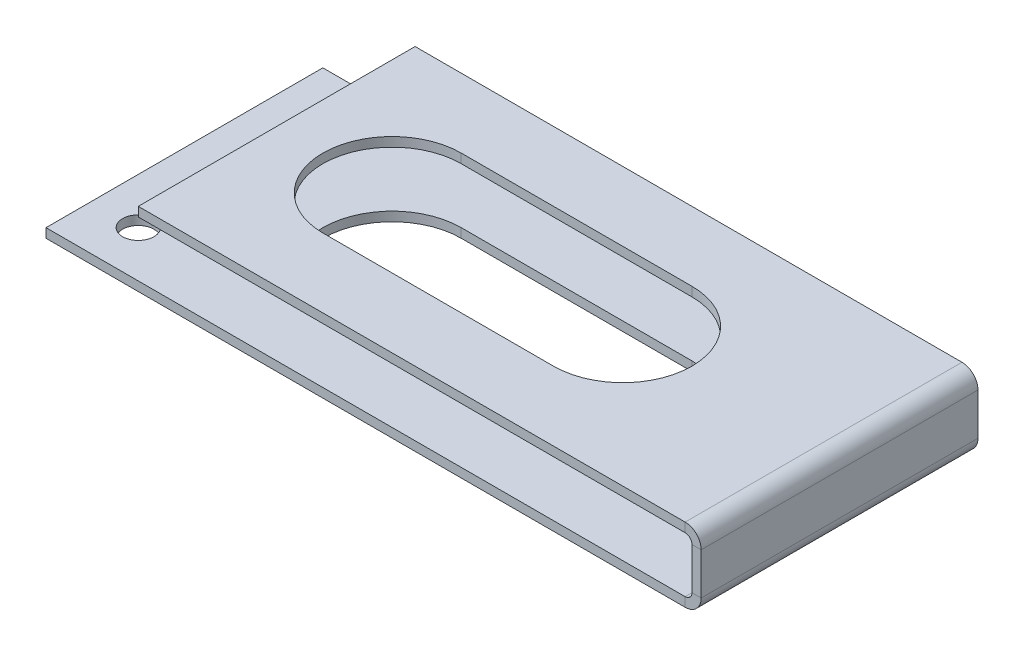
SolidWorks part; units mm, degrees
note: The reader was unsure of these and kept them because the rebuilt part matched: flange length of "Tôle pliée sur arête1", "Tôle pliée sur arête2".
ref_plane "Plan de face" through (0, 0, 0) normal (0, 0, 1) x (1, 0, 0)
ref_plane "Plan de dessus" through (0, 0, 0) normal (0, 1, 0) x (1, 0, 0)
ref_plane "Plan de droite" through (0, 0, 0) normal (1, 0, 0) x (0, 0, -1)
sketch "Esquisse2" plane through (0, 0, 0) normal (0, 1, 0) x (1, 0, 0)
  line L1 (-30, -15) -> (30, -15)
  line L2 (-30, -15) -> (-30, 15)
  line L3 (-30, 15) -> (30, 15)
  line L4 (30, -15) -> (30, 15)
  line L5 (-30, -15) -> (30, 15) construction
  line L6 (-30, 15) -> (30, -15) construction
  line L9 (-7.8646, 0) -> (7.8646, 0) construction
  point P0 (0, 0)
  dimension "D130" = 30
  dimension "D2" = 60
base flange "Tôle de base pliée1" sketch "Esquisse2" thickness 1 reverse thickness direction no parameters "D1"=0.7366
edge flange "Tôle pliée sur arête1" sketch "Esquisse9" flange angle 90 flange length 6 flange position material outside bend radius 0.7366 thickness 1 relief rectangular parameters "D6"=10
sketch "Esquisse9" plane through (30, -1, 0) normal (1, 0, 0) x (0, 0, 1)
  line L2 (-15, 0) -> (-15, 6)
  line L3 (-15, 6) -> (15, 6)
  line L4 (15, 6) -> (15, 0)
  line L7 (15, 0) -> (-15, 0) construction
  line L8 (15, 0) -> (-15, 0)
bend "Pli d'arête1" bend radius 0.7366 bend angle 90 parameters "D5"=1
edge flange "Tôle pliée sur arête2" sketch "Esquisse12" flange angle 90 flange length 70 flange position material outside bend radius 0.7366 thickness 1 relief rectangular parameters "D6"=10
sketch "Esquisse12" plane through (30, -7, 0) normal (0, -1, 0) x (0, 0, 1)
  line L0 (15, 0) -> (-15, 0) construction
  line L1 (15, 0) -> (-15, 0)
  line L2 (-15, 0) -> (-15, 70)
  line L3 (-15, 70) -> (15, 70)
  line L4 (15, 70) -> (15, 0)
bend "Pli d'arête2" bend radius 0.7366 bend angle 90 parameters "D5"=2
sketch "Esquisse26" plane through (0, 0, 0) normal (0, 1, 0) x (1, 0, 0)
  line L0 (-17.5, 0) -> (7.5, 0) construction
  line L1 (-7.8646, 0) -> (7.8646, 0) construction
  line L2 (-17.5, 7.5) -> (7.5, 7.5)
  line L3 (-17.5, -7.5) -> (7.5, -7.5)
  line L5 (-30, 15) -> (-30, -15) construction
  arc A0 (-17.5, 7.5) -> (-17.5, -7.5) centre (-17.5, 0) ccw
  arc A1 (7.5, -7.5) -> (7.5, 7.5) centre (7.5, 0) ccw
  point P5 (-5, 0)
  point P10 (-25, 0)
  point P11 (15, 0)
  dimension "D1" = 40
  dimension "D2" = 15
  dimension "D3" = 5
extrude "Enlèv. mat.-Extru.1" cut sketch "Esquisse26" against normal through all normal cut yes
sketch "Esquisse27" plane through (0, -8, 0) normal (0, 1, 0) x (1, 0, 0)
  line L0 (-35, 15) -> (-35, -15) construction
  line L1 (-30, 15) -> (30, 15) construction
  line L2 (-30, -15) -> (29.2634, -15) construction
  line L3 (-7.8646, 0) -> (7.8646, 0) construction
  line L5 (29.2634, 15) -> (-30, 15) construction
  line L6 (-40, -15) -> (-40, 15) construction
  circle A0 centre (-35, 10) radius 1.7
  circle A1 centre (-35, -10) radius 1.7
  dimension "D2" = 3.4
  dimension "D3" = 5
  dimension "D1" = 5
extrude "Enlèv. mat.-Extru.2" cut sketch "Esquisse27" along normal up to next normal cut yes
sketch "Esquisse29" plane through (0, -7, 0) normal (0, 1, 0) x (1, 0, 0)
  line L0 (-7.8646, 0) -> (7.8646, 0) construction
  line L1 (31, -15) -> (31, 15) construction
  circle A0 centre (26, 0) radius 1.7
  dimension "D1" = 3.4
  dimension "D2" = 5
extrude "Enlèv. mat.-Extru.3" cut sketch "Esquisse29" against normal through all normal cut yes
sketch "Esquisse30" plane through (0, -8, 0) normal (0, -1, 0) x (1, 0, 0)
  line L0 (-5, 7.5) -> (-5, -7.5) construction
  line L1 (-17.5, 7.5) -> (7.5, 7.5) construction
  line L2 (7.5, -7.5) -> (-17.5, -7.5) construction
sketch3d "Esquisse3D2"
  line L0 (-5, -8, 7.5) -> (-5, -8, -7.5) construction
sketch "Lignes de pliage1" [suppressed] plane through (0, 0, 0) normal (0, 1, 0) x (1, 0, 0)
sketch "Cube de visualisation1" [suppressed] plane through (0, 0, 0) normal (0, 1, 0) x (1, 0, 0)
sheet metal parameters "Tôlerie1" thickness 1 parameters "D1"=0.7366
flat pattern "Etat déplié1" [suppressed]
sketch "Lignes de pliage2" plane through (0, 0, 0) normal (0, 1, 0) x (1, 0, 0)
sketch3d "Cube de visualisation2" [suppressed]
  line L0 (-26.75, 15, 0) -> (26.75, 15, 0) construction
  line L1 (-26.75, -15, 0) -> (26.75, -15, 0) construction
  line L2 (-26.75, 15, 0) -> (-26.75, -15, 0) construction
  line L3 (26.75, 15, 0) -> (26.75, -15, 0) construction
sheet metal parameters "Tôlerie2" thickness 1 parameters "D1"=0.7366
flat pattern "Etat déplié1"
sketch "Lignes de pliage2" plane through (0, 0, 0) normal (0, 1, 0) x (1, 0, 0)
  line L0 (26.9846, -15) -> (26.9846, 15) construction
  line L1 (26.9846, -15) -> (26.9846, 15) construction
sketch3d "Cube de visualisation2" [suppressed]
  line L0 (32.2192, 15, 0) -> (-26.75, 15, 0) construction
  line L1 (32.2192, -15, 0) -> (-26.75, -15, 0) construction
  line L2 (32.2192, 15, 0) -> (32.2192, -15, 0) construction
  line L3 (-26.75, 15, 0) -> (-26.75, -15, 0) construction
bend of the flat pattern "Dépliage-<Pli d'arête1>1"
sheet metal parameters "Tôlerie3" thickness 1 parameters "D1"=0.7366
flat pattern "Etat déplié1"
sketch "Lignes de pliage2" plane through (0, 0, 0) normal (0, 1, 0) x (1, 0, 0)
  line L0 (26.9846, -15) -> (26.9846, 15) construction
  line L1 (26.9846, -15) -> (26.9846, 15) construction
  line L2 (32.4539, -15) -> (32.4539, 15) construction
  line L3 (32.4539, -15) -> (32.4539, 15) construction
sketch3d "Cube de visualisation2" [suppressed]
  line L0 (86.1885, 15, 0) -> (-26.75, 15, 0) construction
  line L1 (86.1885, -15, 0) -> (-26.75, -15, 0) construction
  line L2 (86.1885, 15, 0) -> (86.1885, -15, 0) construction
  line L3 (-26.75, 15, 0) -> (-26.75, -15, 0) construction
bend of the flat pattern "Dépliage-<Pli d'arête1>1"
bend of the flat pattern "Dépliage-<Pli d'arête2>1"
sheet metal parameters "Tôlerie7" thickness 1 parameters "D1"=0.7366
flat pattern "Etat déplié1"
sketch "Lignes de pliage2" plane through (0, 0, 0) normal (0, 1, 0) x (1, 0, 0)
  line L0 (26.9846, -15) -> (26.9846, 15) construction
  line L1 (26.9846, -15) -> (26.9846, 15) construction
  line L2 (32.4539, -15) -> (32.4539, 15) construction
  line L3 (32.4539, -15) -> (32.4539, 15) construction
sketch3d "Cube de visualisation2" [suppressed]
  line L0 (86.1885, 15, 0) -> (-26.75, 15, 0) construction
  line L1 (86.1885, -15, 0) -> (-26.75, -15, 0) construction
  line L2 (86.1885, 15, 0) -> (86.1885, -15, 0) construction
  line L3 (-26.75, 15, 0) -> (-26.75, -15, 0) construction
bend of the flat pattern "Dépliage-<Pli d'arête1>1"
bend of the flat pattern "Dépliage-<Pli d'arête2>1"
sheet metal parameters "Tôlerie8" thickness 1 parameters "D1"=0.7366
flat pattern "Etat déplié1"
sketch "Lignes de pliage2" plane through (0, 0, 0) normal (0, 1, 0) x (1, 0, 0)
  line L0 (26.9846, -15) -> (26.9846, 15) construction
  line L1 (26.9846, -15) -> (26.9846, 15) construction
  line L2 (32.4539, -15) -> (32.4539, 15) construction
  line L3 (32.4539, -15) -> (32.4539, 15) construction
sketch3d "Cube de visualisation2" [suppressed]
  line L0 (86.1885, 15, 0) -> (-26.75, 15, 0) construction
  line L1 (86.1885, -15, 0) -> (-26.75, -15, 0) construction
  line L2 (86.1885, 15, 0) -> (86.1885, -15, 0) construction
  line L3 (-26.75, 15, 0) -> (-26.75, -15, 0) construction
bend of the flat pattern "Dépliage-<Pli d'arête1>1"
bend of the flat pattern "Dépliage-<Pli d'arête2>1"
sheet metal parameters "Tôlerie9" thickness 1 parameters "D1"=0.7366
flat pattern "Etat déplié1" [suppressed]
sketch "Lignes de pliage2" plane through (0, 0, 0) normal (0, 1, 0) x (1, 0, 0)
  line L0 (30.2346, -15) -> (30.2346, 15) construction
  line L1 (30.2346, -15) -> (30.2346, 15) construction
  line L2 (36.7039, -15) -> (36.7039, 15) construction
  line L3 (36.7039, -15) -> (36.7039, 15) construction
sketch3d "Cube de visualisation2" [suppressed]
  line L0 (106.9385, 15, 0) -> (-30, 15, 0) construction
  line L1 (106.9385, -15, 0) -> (-30, -15, 0) construction
  line L2 (106.9385, 15, 0) -> (106.9385, -15, 0) construction
  line L3 (-30, 15, 0) -> (-30, -15, 0) construction
bend of the flat pattern "Dépliage-<Pli d'arête1>1"
bend of the flat pattern "Dépliage-<Pli d'arête2>1"
sketch "Esquisse30-1" plane through (66.9385, 0, 0) normal (0, 1, 0) x (-1, 0, 0)
  line L0 (-5, 7.5) -> (-5, -7.5) construction
